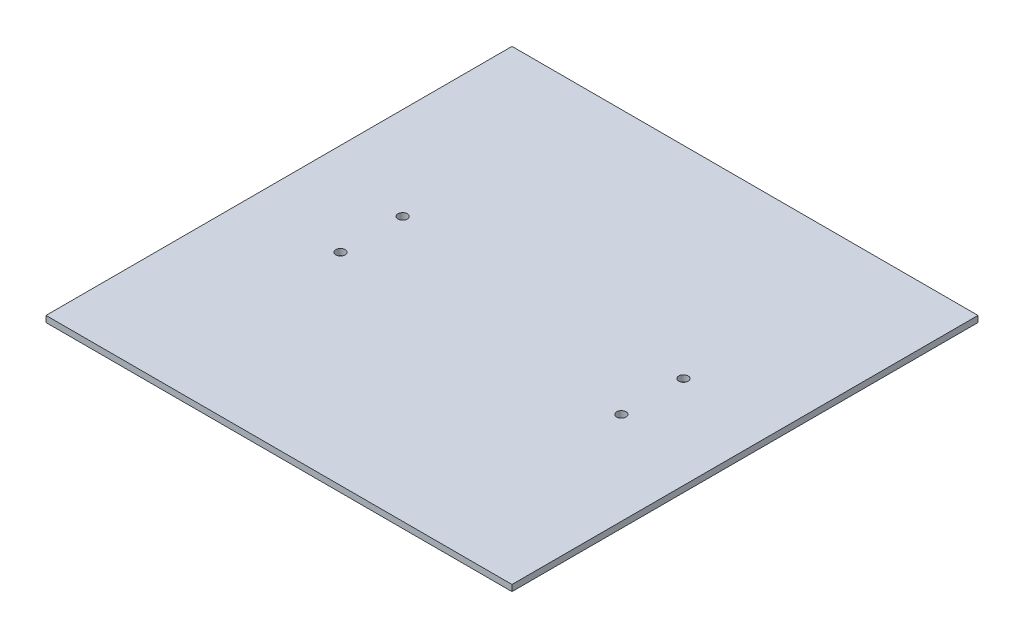
SolidWorks part; units mm, degrees
ref_plane "Front Plane" through (0, 0, 0) normal (0, 0, 1) x (1, 0, 0)
ref_plane "Top Plane" through (0, 0, 0) normal (0, 1, 0) x (1, 0, 0)
ref_plane "Right Plane" through (0, 0, 0) normal (1, 0, 0) x (0, 0, -1)
sketch "Sketch1" plane through (0, 0, 0) normal (0, 1, 0) x (1, 0, 0)
  line L1 (0, 0) -> (150, 0)
  line L2 (0, 0) -> (0, 150)
  line L3 (0, 150) -> (150, 150)
  line L4 (150, 0) -> (150, 150)
  line L5 (29.8, 85) -> (120.2, 85)
  line L6 (29.8, 85) -> (29.8, 65)
  line L7 (29.8, 65) -> (120.2, 65)
  line L8 (120.2, 85) -> (120.2, 65)
  circle A0 centre (29.8, 85) radius 1.5
  circle A1 centre (29.8, 65) radius 1.5
  circle A3 centre (120.2, 85) radius 1.5
  circle A4 centre (120.2, 65) radius 1.5
  dimension "D1" = 150
  dimension "D2" = 150
  dimension "D3" = 20
  dimension "D4" = 90.4
  dimension "D5" = 65
  dimension "D6" = 29.8
  dimension "D7" = 29.8
extrude "Boss-Extrude1" add sketch "Sketch1" along normal blind 2 contours L1 L4 L3 L2 A4 L7 A1 L6 A0 L5 A3 L8 | A4 L8 A3 L5 A0 L6 A1 L7 region at (2.1213, 0, -75) region at (75, 0, -75)
